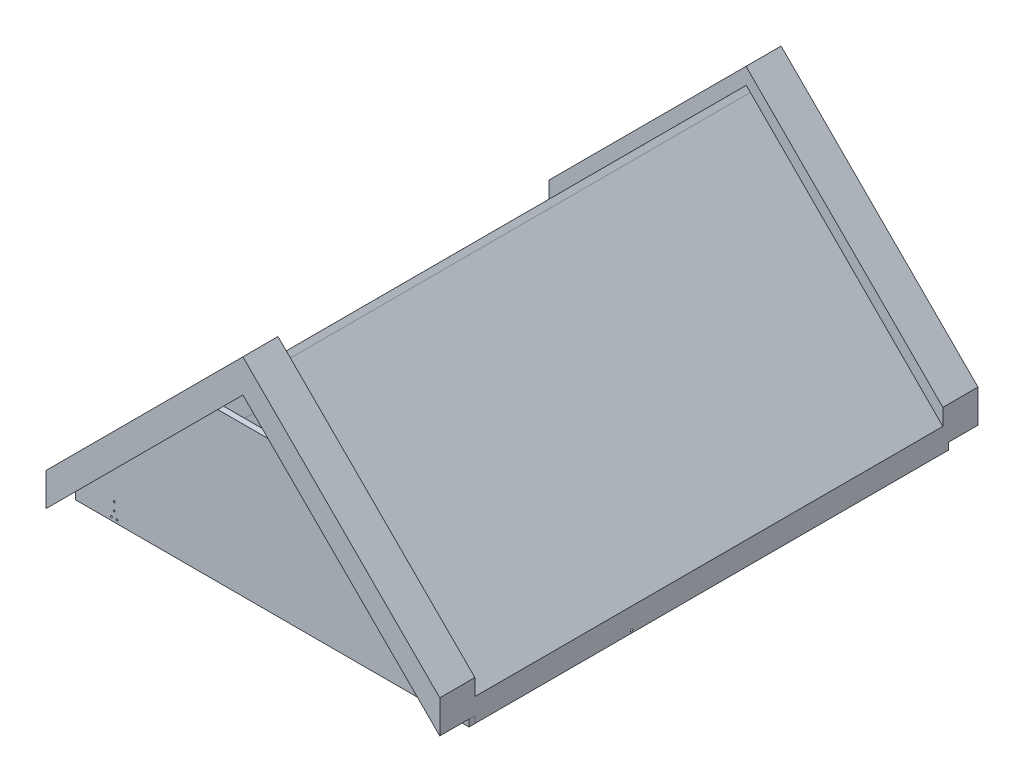
SolidWorks part; units mm, degrees
material "Pine"
ref_plane "Front Plane" through (0, 0, 0) normal (0, 0, 1) x (1, 0, 0)
ref_plane "Top Plane" through (0, 0, 0) normal (0, 1, 0) x (1, 0, 0)
ref_plane "Right Plane" through (0, 0, 0) normal (1, 0, 0) x (0, 0, -1)
sketch "Sketch1" plane through (0, 0, 0) normal (0, 0, 1) x (1, 0, 0)
  line L0 (0, 0) -> (1400, 0)
  line L1 (700, 0) -> (700, 700)
  line L2 (700, 700) -> (0, 0)
  line L3 (700, 700) -> (1400, 0)
  dimension "D1" = 1400
  dimension "D2" = 700
extrude "Boss-Extrude1" add sketch "Sketch1" along normal blind 2000 contours L3 L0 L2
shell "Shell1" thickness 10 removed face at (700, 0, 1000)
sketch "Sketch2" plane through (0, 0, 0) normal (0, -1, 0) x (1, 0, 0)
  line L0 (0, 2000) -> (1400, 2000) construction
  line L1 (-150, 2150) -> (1550, 2150)
  line L2 (-150, 2150) -> (-150, -150)
  line L3 (-150, -150) -> (1550, -150)
  line L4 (1550, 2150) -> (1550, -150)
  line L5 (0, 2000) -> (0, 0) construction
  dimension "D1" = 1700
  dimension "D2" = 2300
  dimension "D3" = 150
  dimension "D4" = 150
sketch "Sketch3" plane through (0, 0, 0) normal (-0.7071, 0.7071, 0) x (0, 0, 1)
  line L10 (2150, 1096.0155) -> (2000, 1096.0155)
  line L11 (2150, 1096.0155) -> (2150, 0)
  line L12 (2150, 0) -> (2000, 0)
  line L13 (2000, 1096.0155) -> (2000, 0)
extrude "Boss-Extrude2" add sketch "Sketch3" along normal blind 100 separate body contours L11 L10 L13 L12
sketch "Sketch7" plane through (700, 700, 0) normal (0.7071, 0.7071, 0) x (0, 0, -1)
  line L5 (-2150, 100) -> (-2000, 100)
  line L6 (-2150, 100) -> (-2150, -989.9495)
  line L7 (-2150, -989.9495) -> (-2000, -989.9495)
  line L8 (-2000, 100) -> (-2000, -989.9495)
extrude "Boss-Extrude4" add sketch "Sketch7" along normal blind 100
sketch "Sketch8" plane through (775, 775, 0) normal (0.7071, 0.7071, 0) x (0, 0, -1)
  line L1 (-2000, 100) -> (-2150, 100)
  line L2 (-2000, 100) -> (-2000, 0)
  line L3 (-2000, 0) -> (-2150, 0)
  line L4 (-2150, 100) -> (-2150, 0)
extrude "Cut-Extrude1" cut sketch "Sketch8" against normal up to vertex (6.066 mm away) and the other way blind 6 up to point (770.7107, 770.7107, 2150)
sketch "Sketch9" plane through (0, 0, 0) normal (-0.7071, -0.7071, 0) x (0, 0, 1)
  line L2 (2000, 100) -> (2150, 100)
  line L3 (2000, 100) -> (2000, 0)
  line L4 (2000, 0) -> (2150, 0)
  line L5 (2150, 100) -> (2150, 0)
extrude "Boss-Extrude5" add sketch "Sketch9" along normal blind 239.05
sketch "Sketch10" plane through (700, -700, 0) normal (0.7071, -0.7071, 0) x (0, 0, -1)
  line L1 (-2000, 989.9495) -> (-2150, 989.9495)
  line L2 (-2000, 989.9495) -> (-2000, 1089.9495)
  line L3 (-2000, 1089.9495) -> (-2150, 1089.9495)
  line L4 (-2150, 989.9495) -> (-2150, 1089.9495)
extrude "Boss-Extrude6" add sketch "Sketch10" along normal blind 399.5
sketch "Sketch13" plane through (0, 0, 2150) normal (0, 0, 1) x (1, 0, 0)
  line L0 (-141.4214, 0) -> (-141.4214, -141.4214)
  line L1 (-150, 0) -> (1550, 0) construction
  line L2 (700, 841.4214) -> (-239.7446, -98.3232) construction
  line L3 (700, 700) -> (-169.0339, -169.0339) construction
  line L4 (-141.4214, -141.4214) -> (-169.0339, -169.0339)
  line L5 (-169.0339, -169.0339) -> (-239.7446, -98.3232)
  line L6 (-239.7446, -98.3232) -> (-141.4214, 0)
  line L7 (1541.4214, 0) -> (1753.1998, -211.7785)
  line L8 (700, 841.4214) -> (1753.1998, -211.7785) construction
  line L9 (1753.1998, -211.7785) -> (1682.4892, -282.4892)
  line L10 (1682.4892, -282.4892) -> (1541.2446, -141.2446)
  line L12 (1541.4214, 0) -> (1541.2446, -141.2446)
extrude "Cut-Extrude4" cut sketch "Sketch13" against normal blind 1197.5
ref_plane "Plane1" through (0, 0, 1000) normal (0, 0, 1) x (1, 0, 0)
mirror "Mirror4" about plane through (0, 0, 1000) normal (0, 0, 1) of bodies 114 108
sketch "Sketch14" plane through (-141.4214, 0, 0) normal (-1, 0, 0) x (0, 0, 1)
  line L0 (0, -141.4214) -> (0, 0) construction
  line L5 (0, -70.7107) -> (2000, -70.7107)
  line L6 (0, -70.7107) -> (0, -170.7107)
  line L7 (0, -170.7107) -> (2000, -170.7107)
  line L8 (2000, -70.7107) -> (2000, -170.7107)
  dimension "D1" = 100
  dimension "D2" = 70.7107
  dimension "D3" = 2000
extrude "Boss-Extrude7" add sketch "Sketch14" against normal blind 25
sketch "Sketch15" plane through (1541.4189, -1.9292, 0) normal (1, -0.0013, 0) x (0, 0, -1)
  line L0 (-2000, 1.9292) -> (-2000, -139.3155) construction
  line L2 (-2000, -68.6932) -> (-2000, -70.8563)
  line L4 (0, -68.6932) -> (0, -70.8563)
  line L6 (-2000, -68.6932) -> (0, -68.6932)
  line L7 (-2000, -68.6932) -> (-2000, -168.6932)
  line L8 (-2000, -168.6932) -> (0, -168.6932)
  line L9 (0, -68.6932) -> (0, -168.6932)
  dimension "D1" = 100
extrude "Boss-Extrude8" add sketch "Sketch15" against normal blind 25 contours L7 L6 L9 L8
ref_plane "Plane2" through (-106.066, -106.066, 0) normal (0.7071, 0.7071, 0) x (0, 0, -1)
sketch "Sketch16" plane through (-106.066, -106.066, 0) normal (0.7071, 0.7071, 0) x (0, 0, -1)
  line L0 (0, -1089.9495) -> (0, 100) construction
  line L1 (-2000, 50) -> (0, 50)
  line L2 (-2000, 50) -> (-2000, 25)
  line L3 (-2000, 25) -> (0, 25)
  line L4 (0, 50) -> (0, 25)
  line L5 (-2000, 50) -> (0, 50) construction
  dimension "D1" = 25
  dimension "D2" = 2000
extrude "Boss-Extrude9" add sketch "Sketch16" along normal blind 1436
ref_plane "Plane3" through (804.0484, -806.0636, 0) normal (-0.7062, 0.708, 0) x (0.708, 0.7062, 0)
sketch "Sketch17" plane through (804.0484, -806.0636, 0) normal (-0.7062, 0.708, 0) x (0.708, 0.7062, 0)
  line L0 (1091.3128, 0) -> (1089.9174, 0) construction
  line L1 (1041.3752, 0) -> (1016.3752, 0)
  line L2 (1041.3752, 0) -> (1041.3752, -2000)
  line L3 (1041.3752, -2000) -> (1016.3752, -2000)
  line L4 (1016.3752, 0) -> (1016.3752, -2000)
  dimension "D1" = 25
  dimension "D2" = 2000
extrude "Boss-Extrude10" add sketch "Sketch17" along normal blind 1436
sketch "Sketch25" plane through (-35.3553, 35.3553, 0) normal (-0.7071, 0.7071, 0) x (0, 0, 1)
  line L6 (0, 1041.4386) -> (2000, 1041.4386)
  line L7 (2000, 1041.4386) -> (2000, 1089.9495)
  line L8 (2000, 1089.9495) -> (2000, 1286)
  line L9 (2000, 1286) -> (0, 1286)
  line L10 (0, 1286) -> (0, 1089.9495)
  line L11 (0, 1089.9495) -> (0, 1041.4386)
  line L12 (0, 1041.4386) -> (2000, 1041.4386)
  line L13 (2000, 1041.4386) -> (2000, 1089.9495)
  line L14 (2000, 1089.9495) -> (2000, 1286)
  line L15 (2000, 1286) -> (0, 1286)
  line L16 (0, 1286) -> (0, 1089.9495)
  line L17 (0, 1089.9495) -> (0, 1041.4386)
  dimension "D1" = 0
sketch "Sketch26" plane through (737.2845, 735.4413, 0) normal (0.708, 0.7062, 0) x (0, 0, -1)
  line L6 (-2000, 101.3034) -> (-2000, 51.3034)
  line L7 (-2000, 51.3034) -> (0, 51.3034)
  line L8 (0, 51.3034) -> (0, 101.3034)
  line L9 (0, 101.3034) -> (0, 297.478)
  line L10 (0, 297.478) -> (-2000, 297.478)
  line L11 (-2000, 297.478) -> (-2000, 101.3034)
  line L12 (-2000, 101.3034) -> (-2000, 51.3034)
  line L14 (0, 51.3034) -> (0, 101.3034)
  line L15 (0, 101.3034) -> (0, 297.478)
  line L16 (0, 297.478) -> (-2000, 297.478)
  line L17 (-2000, 297.478) -> (-2000, 101.3034)
  line L18 (-2000, 51.3034) -> (0, 51.3034)
  dimension "D1" = 0
sketch "Sketch27" plane through (719.5847, 717.7858, 0) normal (-0.708, -0.7062, 0) x (0, 0, 1)
  line L6 (0, 101.2721) -> (0, 51.2721)
  line L7 (0, 51.2721) -> (2000, 51.2721)
  line L8 (2000, 51.2721) -> (2000, 101.2721)
  line L9 (2000, 101.2721) -> (2000, 297.478)
  line L10 (2000, 297.478) -> (0, 297.478)
  line L11 (0, 297.478) -> (0, 101.2721)
  line L12 (0, 101.2721) -> (0, 51.2721)
  line L13 (0, 51.2721) -> (2000, 51.2721)
  line L14 (2000, 51.2721) -> (2000, 101.2721)
  line L15 (2000, 101.2721) -> (2000, 297.478)
  line L16 (2000, 297.478) -> (0, 297.478)
  line L17 (0, 297.478) -> (0, 101.2721)
  dimension "D1" = 0
extrude "Cut-Extrude11" cut sketch "Sketch27" against normal blind 1286
sketch "Sketch28" plane through (-17.6777, 17.6777, 0) normal (0.7071, -0.7071, 0) x (0, 0, -1)
  line L6 (-2000, 1041.4073) -> (0, 1041.4073)
  line L7 (0, 1041.4073) -> (0, 1089.9495)
  line L8 (0, 1089.9495) -> (0, 1286)
  line L9 (0, 1286) -> (-2000, 1286)
  line L10 (-2000, 1286) -> (-2000, 1089.9495)
  line L11 (-2000, 1089.9495) -> (-2000, 1041.4073)
  line L12 (-2000, 1041.4073) -> (0, 1041.4073)
  line L13 (0, 1041.4073) -> (0, 1089.9495)
  line L14 (0, 1089.9495) -> (0, 1286)
  line L15 (0, 1286) -> (-2000, 1286)
  line L16 (-2000, 1286) -> (-2000, 1089.9495)
  line L17 (-2000, 1089.9495) -> (-2000, 1041.4073)
  dimension "D1" = 0
extrude "Cut-Extrude12" cut sketch "Sketch28" against normal blind 1286
sketch "Sketch29" plane through (0, 0, 2000) normal (0, 0, -1) x (-1, 0, 0)
  line L1 (-701.0308, 594.9648) -> (-1466.5902, -170.5946)
  line L2 (-630.3202, 665.6755) -> (116.4214, -81.066)
  line L4 (-701.0308, 594.9648) -> (64.6409, -170.7069)
  line L5 (116.4214, -170.7107) -> (64.6409, -170.7069)
  line L6 (116.4214, -81.066) -> (-701.0308, 736.3862)
  line L7 (-701.0308, 736.3862) -> (-1516.32, -80.9463)
  line L8 (-1516.32, -80.9463) -> (-1516.2758, -116.2758)
  line L9 (-1516.2758, -116.2758) -> (-700, 700)
  line L10 (-700, 700) -> (116.4214, -116.4214)
  line L11 (116.4214, -116.4214) -> (116.4214, -81.066)
  line L12 (-630.3202, 665.6755) -> (-701.0308, 736.3862)
  line L13 (-701.0308, 736.3862) -> (-1516.32, -80.9463)
  line L18 (-1466.5902, -170.5946) -> (-1516.2078, -170.5909)
  line L19 (-1516.32, -80.9463) -> (-1516.2078, -170.5909)
  line L20 (116.4214, -81.066) -> (116.4214, -170.7107)
  dimension "D2" = 100
  dimension "D3" = 100
  dimension "D1" = 0
extrude "Boss-Extrude13" add sketch "Sketch29" along normal blind 50
ref_plane "Plane4" through (0, 0, 1359) normal (0, 0, -1) x (-1, 0, 0)
sketch "Sketch30" plane through (0, 0, 1359) normal (0, 0, -1) x (-1, 0, 0)
  line L8 (-701.0308, 736.3862) -> (-1516.32, -80.9463)
  line L9 (-701.0308, 736.3862) -> (-1516.32, -80.9463)
  line L10 (-1516.2078, -170.5909) -> (-1466.5902, -170.5946)
  line L11 (-1466.5902, -170.5946) -> (-701.0308, 594.9648)
  line L12 (-701.0308, 594.9648) -> (64.6409, -170.7069)
  line L13 (64.6409, -170.7069) -> (116.4214, -170.7107)
  line L14 (-1516.32, -80.9463) -> (-1516.2078, -170.5909)
  line L15 (-1516.32, -80.9463) -> (-1516.2078, -170.5909)
  line L18 (-1516.2078, -170.5909) -> (-1466.5902, -170.5946)
  line L19 (-1466.5902, -170.5946) -> (-701.0308, 594.9648)
  line L20 (-701.0308, 594.9648) -> (64.6409, -170.7069)
  line L21 (64.6409, -170.7069) -> (116.4214, -170.7107)
  line L24 (116.4214, -170.7107) -> (116.4214, -81.066)
  line L25 (116.4214, -170.7107) -> (116.4214, -81.066)
  line L26 (116.4214, -81.066) -> (-701.0308, 736.3862)
  line L27 (116.4214, -81.066) -> (-701.0308, 736.3862)
  dimension "D1" = 0
extrude "Boss-Extrude14" add sketch "Sketch30" along normal blind 50
ref_plane "Plane5" through (0, 0, 691) normal (0, 0, -1) x (-1, 0, 0)
sketch "Sketch31" plane through (0, 0, 691) normal (0, 0, -1) x (-1, 0, 0)
  line L8 (116.4214, -81.066) -> (-701.0308, 736.3862)
  line L9 (-701.0308, 736.3862) -> (-1516.32, -80.9463)
  line L10 (-1516.32, -80.9463) -> (-1516.2078, -170.5909)
  line L11 (-1516.2078, -170.5909) -> (-1466.5902, -170.5946)
  line L12 (-1466.5902, -170.5946) -> (-701.0308, 594.9648)
  line L13 (-701.0308, 594.9648) -> (64.6409, -170.7069)
  line L14 (64.6409, -170.7069) -> (116.4214, -170.7107)
  line L15 (116.4214, -170.7107) -> (116.4214, -81.066)
  line L16 (116.4214, -81.066) -> (-701.0308, 736.3862)
  line L17 (-701.0308, 736.3862) -> (-1516.32, -80.9463)
  line L18 (-1516.32, -80.9463) -> (-1516.2078, -170.5909)
  line L19 (-1516.2078, -170.5909) -> (-1466.5902, -170.5946)
  line L20 (-1466.5902, -170.5946) -> (-701.0308, 594.9648)
  line L21 (-701.0308, 594.9648) -> (64.6409, -170.7069)
  line L22 (64.6409, -170.7069) -> (116.4214, -170.7107)
  line L23 (116.4214, -170.7107) -> (116.4214, -81.066)
  dimension "D1" = 0
extrude "Boss-Extrude15" add sketch "Sketch31" along normal blind 50
ref_plane "Plane6" through (0, 0, 50) normal (0, 0, -1) x (-1, 0, 0)
sketch "Sketch33" plane through (0, 0, 50) normal (0, 0, -1) x (-1, 0, 0)
  line L8 (116.4214, -170.7107) -> (116.4214, -81.066)
  line L9 (116.4214, -81.066) -> (-701.0308, 736.3862)
  line L10 (-701.0308, 736.3862) -> (-1516.32, -80.9463)
  line L11 (-1516.32, -80.9463) -> (-1516.2078, -170.5909)
  line L12 (-1516.2078, -170.5909) -> (-1466.5902, -170.5946)
  line L13 (-1466.5902, -170.5946) -> (-701.0308, 594.9648)
  line L14 (-701.0308, 594.9648) -> (64.6409, -170.7069)
  line L15 (64.6409, -170.7069) -> (116.4214, -170.7107)
  line L16 (116.4214, -170.7107) -> (116.4214, -81.066)
  line L17 (116.4214, -81.066) -> (-701.0308, 736.3862)
  line L18 (-701.0308, 736.3862) -> (-1516.32, -80.9463)
  line L19 (-1516.32, -80.9463) -> (-1516.2078, -170.5909)
  line L20 (-1516.2078, -170.5909) -> (-1466.5902, -170.5946)
  line L21 (-1466.5902, -170.5946) -> (-701.0308, 594.9648)
  line L22 (-701.0308, 594.9648) -> (64.6409, -170.7069)
  line L23 (64.6409, -170.7069) -> (116.4214, -170.7107)
  dimension "D1" = 0
extrude "Boss-Extrude16" add sketch "Sketch33" along normal blind 50
sketch "Sketch35" plane through (0, 0, 2000) normal (0, 0, 1) x (1, 0, 0)
  line L0 (60.3572, -45.7088) -> (1341.7044, -45.7088)
  line L1 (701.0308, 594.9648) -> (-64.6409, -170.7069) construction
  line L2 (-39.6428, -145.7088) -> (1441.7044, -145.7088)
  line L3 (1466.5902, -170.5946) -> (701.0308, 594.9648) construction
  line L4 (60.3572, -45.7088) -> (-39.6428, -145.7088)
  line L5 (1341.7044, -45.7088) -> (1441.7044, -145.7088)
  line L9 (-64.6409, -170.7069) -> (-116.4214, -170.7107) construction
  line L10 (-64.6409, -170.7069) -> (-116.4214, -170.7107)
  point P10 (-90.5311, -170.7088)
  line M8 (-64.6409, -170.7069) -> (701.0308, 594.9648)
  line M9 (701.0308, 594.9648) -> (1466.5902, -170.5946)
  dimension "D1" = 100
  dimension "D2" = 25
extrude "Boss-Extrude17" add sketch "Sketch35" against normal blind 50 separate body contours L2 L0 M8 M9 region at (701.0308, -96.9153, 2000)
sketch "Sketch36" plane through (0, 0, 1359) normal (0, 0, -1) x (-1, 0, 0)
  line L4 (39.6428, -145.7088) -> (-60.3572, -45.7088)
  line L5 (-60.3572, -45.7088) -> (-1341.7044, -45.7088)
  line L6 (-1341.7044, -45.7088) -> (-1441.7044, -145.7088)
  line L7 (-1441.7044, -145.7088) -> (39.6428, -145.7088)
  line L8 (39.6428, -145.7088) -> (-60.3572, -45.7088)
  line L9 (-60.3572, -45.7088) -> (-1341.7044, -45.7088)
  line L10 (-1341.7044, -45.7088) -> (-1441.7044, -145.7088)
  line L11 (-1441.7044, -145.7088) -> (39.6428, -145.7088)
  dimension "D1" = 0
extrude "Boss-Extrude18" add sketch "Sketch36" along normal blind 50 separate body
sketch "Sketch37" plane through (0, 0, 691) normal (0, 0, -1) x (-1, 0, 0)
  line L4 (-1441.7044, -145.7088) -> (39.6428, -145.7088)
  line L5 (39.6428, -145.7088) -> (-60.3572, -45.7088)
  line L6 (-60.3572, -45.7088) -> (-1341.7044, -45.7088)
  line L7 (-1341.7044, -45.7088) -> (-1441.7044, -145.7088)
  line L8 (-1441.7044, -145.7088) -> (39.6428, -145.7088)
  line L9 (39.6428, -145.7088) -> (-60.3572, -45.7088)
  line L10 (-60.3572, -45.7088) -> (-1341.7044, -45.7088)
  line L11 (-1341.7044, -45.7088) -> (-1441.7044, -145.7088)
  dimension "D1" = 0
extrude "Boss-Extrude19" add sketch "Sketch37" along normal blind 50 separate body
sketch "Sketch38" plane through (0, 0, 50) normal (0, 0, -1) x (-1, 0, 0)
  line L4 (-1341.7044, -45.7088) -> (-1441.7044, -145.7088)
  line L5 (-1441.7044, -145.7088) -> (39.6428, -145.7088)
  line L6 (39.6428, -145.7088) -> (-60.3572, -45.7088)
  line L7 (-60.3572, -45.7088) -> (-1341.7044, -45.7088)
  line L8 (-1341.7044, -45.7088) -> (-1441.7044, -145.7088)
  line L9 (-1441.7044, -145.7088) -> (39.6428, -145.7088)
  line L10 (39.6428, -145.7088) -> (-60.3572, -45.7088)
  line L11 (-60.3572, -45.7088) -> (-1341.7044, -45.7088)
  dimension "D1" = 0
extrude "Boss-Extrude20" add sketch "Sketch38" along normal blind 50 separate body
sketch "Sketch34" plane through (0.0125, -170.7021, 0) normal (0.0001, -1, 0) x (1, 0.0001, 0)
  line L0 (1441.6938, 1950) -> (1441.6938, 2000) construction
  line L5 (1.0188, 2000) -> (1401.0188, 2000)
  line L6 (1.0188, 2000) -> (1.0188, 0)
  line L7 (1.0188, 0) -> (1401.0188, 0)
  line L8 (1401.0188, 2000) -> (1401.0188, 0)
  line L9 (-39.6534, 2000) -> (1441.6938, 2000) construction
  dimension "D1" = 1400
  dimension "D2" = 2000
  dimension "D3" = 40.675
extrude "Boss-Extrude21" add sketch "Sketch34" against normal blind 25 separate body
sketch "Sketch39" plane through (0, 0, 2000) normal (0, 0, 1) x (1, 0, 0)
  line L0 (-64.6409, -170.7069) -> (1466.5902, -170.5946)
  line L1 (467.5, 467.5) -> (932.5, 467.5)
  line L10 (-141.4214, -170.7107) -> (-116.4214, -170.7107)
  line L11 (-116.4214, -170.7107) -> (-64.6409, -170.7069)
  line L12 (-64.6409, -170.7069) -> (701.0308, 594.9648)
  line L13 (701.0308, 594.9648) -> (1466.5902, -170.5946)
  line L14 (1466.5902, -170.5946) -> (1516.2078, -170.5909)
  line L15 (1516.2078, -170.5909) -> (1541.2078, -170.6222)
  line L16 (1541.2078, -170.6222) -> (1541.2446, -141.2446)
  line L17 (1541.2446, -141.2446) -> (700, 700)
  line L18 (700, 700) -> (-141.4214, -141.4214)
  line L19 (-141.4214, -141.4214) -> (-141.4214, -170.7107)
  line L20 (-141.4214, -170.7107) -> (-116.4214, -170.7107)
  line L21 (-116.4214, -170.7107) -> (-64.6409, -170.7069)
  line L24 (1466.5902, -170.5946) -> (1516.2078, -170.5909)
  line L25 (1516.2078, -170.5909) -> (1541.2078, -170.6222)
  line L26 (1541.2078, -170.6222) -> (1541.2446, -141.2446)
  line L27 (1541.2446, -141.2446) -> (932.5, 467.5)
  line L28 (467.5, 467.5) -> (-141.4214, -141.4214)
  line L29 (-141.4214, -141.4214) -> (-141.4214, -170.7107)
  dimension "D2" = 465
  dimension "D1" = 0
extrude "Boss-Extrude22" add sketch "Sketch39" along normal blind 25 separate body
sketch "Sketch40" plane through (0, 0, 0) normal (0, 0, -1) x (-1, 0, 0)
  line L0 (-1466.5902, -170.5946) -> (64.6409, -170.7069)
  line L2 (-932.5, 467.5) -> (-467.5, 467.5)
  line L10 (141.4214, -170.7107) -> (141.4214, -141.4214)
  line L11 (141.4214, -141.4214) -> (-700, 700)
  line L12 (-700, 700) -> (-1541.2446, -141.2446)
  line L13 (-1541.2446, -141.2446) -> (-1541.2078, -170.6222)
  line L14 (-1541.2078, -170.6222) -> (-1516.2078, -170.5909)
  line L15 (-1516.2078, -170.5909) -> (-1466.5902, -170.5946)
  line L16 (-1466.5902, -170.5946) -> (-701.0308, 594.9648)
  line L17 (-701.0308, 594.9648) -> (64.6409, -170.7069)
  line L18 (64.6409, -170.7069) -> (116.4214, -170.7107)
  line L19 (116.4214, -170.7107) -> (141.4214, -170.7107)
  line L20 (141.4214, -170.7107) -> (141.4214, -141.4214)
  line L21 (141.4214, -141.4214) -> (-467.5, 467.5)
  line L22 (-932.5, 467.5) -> (-1541.2446, -141.2446)
  line L23 (-1541.2446, -141.2446) -> (-1541.2078, -170.6222)
  line L24 (-1541.2078, -170.6222) -> (-1516.2078, -170.5909)
  line L25 (-1516.2078, -170.5909) -> (-1466.5902, -170.5946)
  line L28 (64.6409, -170.7069) -> (116.4214, -170.7107)
  line L29 (116.4214, -170.7107) -> (141.4214, -170.7107)
  dimension "D2" = 465
  dimension "D1" = 0
extrude "Boss-Extrude23" add sketch "Sketch40" along normal blind 25
sketch "Sketch41" plane through (0.0125, -170.7021, 0) normal (0.0001, -1, 0) x (1, 0.0001, 0)
  line L0 (12.3035, 1864.4107) -> (16.9035, 1864.4244)
  line L1 (1.0015, 1999.9778) -> (12.3035, 1864.4107)
  line L2 (0.9765, 2008.4278) -> (1.0015, 1999.9778)
  line L3 (9.9764, 2008.4544) -> (0.9765, 2008.4278)
  line L4 (10.0015, 2000.0045) -> (9.9764, 2008.4544)
  line L5 (27.8014, 2000.0573) -> (10.0015, 2000.0045)
  line L6 (27.7764, 2008.5072) -> (27.8014, 2000.0573)
  line L7 (36.7763, 2008.5339) -> (27.7764, 2008.5072)
  line L8 (36.8014, 2000.084) -> (36.7763, 2008.5339)
  line L9 (26.3034, 1864.4523) -> (36.8014, 2000.084)
  line L10 (21.7034, 1864.4386) -> (26.3034, 1864.4523)
  line L77 (1376.4806, 1864.3486) -> (1381.0806, 1864.3622)
  line L78 (1365.1787, 1999.9157) -> (1376.4806, 1864.3486)
  line L79 (1365.1536, 2008.3656) -> (1365.1787, 1999.9157)
  line L80 (1374.1536, 2008.3923) -> (1365.1536, 2008.3656)
  line L81 (1374.1786, 1999.9423) -> (1374.1536, 2008.3923)
  line L82 (1391.9786, 1999.9951) -> (1374.1786, 1999.9423)
  line L83 (1391.9535, 2008.445) -> (1391.9786, 1999.9951)
  line L84 (1400.9535, 2008.4717) -> (1391.9535, 2008.445)
  line L85 (1400.9785, 2000.0218) -> (1400.9535, 2008.4717)
  line L86 (1390.4806, 1864.3901) -> (1400.9785, 2000.0218)
  line L87 (1385.8806, 1864.3764) -> (1390.4806, 1864.3901)
  spline S0 degree 3 poles (27.8669, 1977.9724) (22.8369, 1977.9575) (22.8518, 1972.9275) (27.8818, 1972.9424) (32.9118, 1972.9573) (32.8969, 1977.9873) (27.8669, 1977.9724) (22.8369, 1977.9575) (22.8518, 1972.9275) knots -0.5 0 0 0 0.5 0.5 0.5 1 1 1 1.5 1.5 1.5 weights 1 0.333333 0.333333 1 0.333333 0.333333 1 0.333333 0.333333 only from (27.8669, 1977.9724) to (27.8669, 1977.9724)
  spline S1 degree 3 poles (19.1096, 1929.8312) (14.3096, 1929.817) (14.3238, 1925.017) (19.1238, 1925.0312) (23.9238, 1925.0455) (23.9095, 1929.8454) (19.1096, 1929.8312) (14.3096, 1929.817) (14.3238, 1925.017) knots -0.5 0 0 0 0.5 0.5 0.5 1 1 1 1.5 1.5 1.5 weights 1 0.333333 0.333333 1 0.333333 0.333333 1 0.333333 0.333333 only from (19.1096, 1929.8312) to (19.1096, 1929.8312)
  spline S32 degree 3 poles (19.2519, 1881.8314) (14.4519, 1881.8172) (14.4661, 1877.0172) (19.2661, 1877.0314) (24.0661, 1877.0457) (24.0518, 1881.8457) (19.2519, 1881.8314) (14.4519, 1881.8172) (14.4661, 1877.0172) knots -0.5 0 0 0 0.5 0.5 0.5 1 1 1 1.5 1.5 1.5 weights 1 0.333333 0.333333 1 0.333333 0.333333 1 0.333333 0.333333 only from (19.2519, 1881.8314) to (19.2519, 1881.8314)
  spline S33 degree 3 poles (10.0366, 1988.1686) (4.5086, 1988.1522) (4.525, 1982.6242) (10.053, 1982.6406) (15.581, 1982.657) (15.5646, 1988.185) (10.0366, 1988.1686) (4.5086, 1988.1522) (4.525, 1982.6242) knots -0.5 0 0 0 0.5 0.5 0.5 1 1 1 1.5 1.5 1.5 weights 1 0.333333 0.333333 1 0.333333 0.333333 1 0.333333 0.333333 only from (10.0366, 1988.1686) to (10.0366, 1988.1686)
  spline S34 degree 3 poles (16.9035, 1864.4244) (16.9177, 1859.6244) (21.7177, 1859.6386) (21.7034, 1864.4386) knots 0 0 0 0 1 1 1 1 weights 1 0.333333 0.333333 1
  spline S35 degree 3 poles (1392.044, 1977.9102) (1387.014, 1977.8953) (1387.029, 1972.8653) (1392.0589, 1972.8802) (1397.0889, 1972.8951) (1397.074, 1977.9251) (1392.044, 1977.9102) (1387.014, 1977.8953) (1387.029, 1972.8653) knots -0.5 0 0 0 0.5 0.5 0.5 1 1 1 1.5 1.5 1.5 weights 1 0.333333 0.333333 1 0.333333 0.333333 1 0.333333 0.333333 only from (1392.044, 1977.9102) to (1392.044, 1977.9102)
  spline S36 degree 3 poles (1383.2867, 1929.769) (1378.4867, 1929.7548) (1378.501, 1924.9548) (1383.3009, 1924.969) (1388.1009, 1924.9833) (1388.0867, 1929.7833) (1383.2867, 1929.769) (1378.4867, 1929.7548) (1378.501, 1924.9548) knots -0.5 0 0 0 0.5 0.5 0.5 1 1 1 1.5 1.5 1.5 weights 1 0.333333 0.333333 1 0.333333 0.333333 1 0.333333 0.333333 only from (1383.2867, 1929.769) to (1383.2867, 1929.769)
  spline S37 degree 3 poles (1383.429, 1881.7692) (1378.629, 1881.755) (1378.6433, 1876.955) (1383.4432, 1876.9693) (1388.2432, 1876.9835) (1388.229, 1881.7835) (1383.429, 1881.7692) (1378.629, 1881.755) (1378.6433, 1876.955) knots -0.5 0 0 0 0.5 0.5 0.5 1 1 1 1.5 1.5 1.5 weights 1 0.333333 0.333333 1 0.333333 0.333333 1 0.333333 0.333333 only from (1383.429, 1881.7692) to (1383.429, 1881.7692)
  spline S38 degree 3 poles (1374.2137, 1988.1064) (1368.6857, 1988.09) (1368.7021, 1982.562) (1374.2301, 1982.5784) (1379.7581, 1982.5948) (1379.7417, 1988.1228) (1374.2137, 1988.1064) (1368.6857, 1988.09) (1368.7021, 1982.562) knots -0.5 0 0 0 0.5 0.5 0.5 1 1 1 1.5 1.5 1.5 weights 1 0.333333 0.333333 1 0.333333 0.333333 1 0.333333 0.333333 only from (1374.2137, 1988.1064) to (1374.2137, 1988.1064)
  spline S39 degree 3 poles (1381.0806, 1864.3622) (1381.0948, 1859.5622) (1385.8948, 1859.5764) (1385.8806, 1864.3764) knots 0 0 0 0 1 1 1 1 weights 1 0.333333 0.333333 1
extrude "Cut-Extrude14" [suppressed] cut sketch "Sketch41" against normal blind 10 contours S33 | S0 | S1 | S36 | S35 | S38
ref_plane "Plane7" through (0, 0, 2010) normal (0, 0, 1) x (1, 0, 0)
sketch "Sketch42" plane through (0, 0, 2010) normal (0, 0, 1) x (-1, 0, 0)
  line L88 (-1349.3821, 25.2633) -> (-1353.982, 25.2497)
  line L89 (-1353.982, 25.2497) -> (-1362.944, 132.749)
  line L90 (-1362.944, 132.749) -> (-1363.0523, 169.2734)
  line L91 (-1363.0523, 169.2734) -> (-1356.3091, 169.2934)
  line L92 (-1356.3091, 169.2934) -> (-1356.284, 160.8434)
  line L93 (-1356.284, 160.8434) -> (-1338.5085, 160.8961)
  line L94 (-1338.5085, 160.8961) -> (-1338.5336, 169.3595)
  line L95 (-1331.5821, 133.8178) -> (-1339.9821, 25.2912)
  line L96 (-1339.9821, 25.2912) -> (-1344.5821, 25.2775)
  line L97 (-1331.5821, 133.8178) -> (-1331.7903, 169.3595)
  line L99 (-1331.7903, 169.3595) -> (-1338.5336, 169.3595)
  spline S2 degree 3 poles (-1344.5821, 25.2775) (-1344.5679, 20.4775) (-1349.3678, 20.4633) (-1349.3821, 25.2633) knots 0 0 0 0 1 1 1 1 weights 1 0.333333 0.333333 1
  spline S3 degree 3 poles (-1338.449, 149.0603) (-1332.921, 149.0766) (-1332.9047, 143.5487) (-1338.4326, 143.5323) (-1343.9606, 143.5159) (-1343.977, 149.0439) (-1338.449, 149.0603) (-1332.921, 149.0766) (-1332.9047, 143.5487) knots -0.5 0 0 0 0.5 0.5 0.5 1 1 1 1.5 1.5 1.5 weights 1 0.333333 0.333333 1 0.333333 0.333333 1 0.333333 0.333333 only from (-1338.449, 149.0603) to (-1338.449, 149.0603)
  spline S4 degree 3 poles (-1347.0337, 42.6703) (-1342.2337, 42.6846) (-1342.2194, 37.8846) (-1347.0194, 37.8704) (-1351.8194, 37.8561) (-1351.8336, 42.6561) (-1347.0337, 42.6703) (-1342.2337, 42.6846) (-1342.2194, 37.8846) knots -0.5 0 0 0 0.5 0.5 0.5 1 1 1 1.5 1.5 1.5 weights 1 0.333333 0.333333 1 0.333333 0.333333 1 0.333333 0.333333 only from (-1347.0337, 42.6703) to (-1347.0337, 42.6703)
  spline S5 degree 3 poles (-1347.176, 90.6701) (-1342.376, 90.6844) (-1342.3617, 85.8844) (-1347.1617, 85.8701) (-1351.9617, 85.8559) (-1351.9759, 90.6559) (-1347.176, 90.6701) (-1342.376, 90.6844) (-1342.3617, 85.8844) knots -0.5 0 0 0 0.5 0.5 0.5 1 1 1 1.5 1.5 1.5 weights 1 0.333333 0.333333 1 0.333333 0.333333 1 0.333333 0.333333 only from (-1347.176, 90.6701) to (-1347.176, 90.6701)
  spline S6 degree 3 poles (-1356.2186, 138.7585) (-1351.1886, 138.7734) (-1351.1737, 133.7435) (-1356.2036, 133.7285) (-1361.2336, 133.7136) (-1361.2485, 138.7436) (-1356.2186, 138.7585) (-1351.1886, 138.7734) (-1351.1737, 133.7435) knots -0.5 0 0 0 0.5 0.5 0.5 1 1 1 1.5 1.5 1.5 weights 1 0.333333 0.333333 1 0.333333 0.333333 1 0.333333 0.333333 only from (-1356.2186, 138.7585) to (-1356.2186, 138.7585)
  dimension "D1" = 1331.5821
  dimension "D2" = 1331.7903
  dimension "D3" = 1338.449
  dimension "D4" = 1338.5085
  dimension "D5" = 1338.5336
  dimension "D6" = 1339.9821
  dimension "D7" = 1344.5821
  dimension "D8" = 1347.0337
  dimension "D9" = 1347.176
  dimension "D10" = 1349.3821
  dimension "D11" = 1356.3091
  dimension "D12" = 1356.2186
  dimension "D13" = 1356.284
  dimension "D14" = 1363.0523
  dimension "D15" = 1362.944
  dimension "D16" = 25.2497
  dimension "D17" = 132.749
  dimension "D18" = 149.0603
  dimension "D20" = 42.6703
  dimension "D21" = 90.6701
  dimension "D23" = 133.8178
extrude "Cut-Extrude15" [suppressed] cut sketch "Sketch42" against normal blind 20
sketch "Sketch43" plane through (0, 0, 0) normal (1, 0, 0) x (0, 0, -1)
  line L0 (-2000, -170.6222) -> (25, -170.6222) construction
  line L1 (-2150, 0) -> (-2150, -141.2446) construction
  circle A0 centre (-1330, -160.6222) radius 5
  dimension "D1" = 10
  dimension "D2" = 10
  dimension "D3" = 820
extrude "Cut-Extrude16" cut sketch "Sketch43" against normal through all both and the other way through all
sketch "Sketch45" plane through (0, 0, 2000) normal (0, 0, 1) x (1, 0, 0)
  line L0 (1.0294, -145.7021) -> (1.0313, -170.7021) construction
  line L1 (13.0316, -156.2021) -> (37.0316, -156.2021) construction
  line L2 (5.0316, -175.7021) -> (45.0316, -175.7021) construction
  line L3 (25.0316, -175.7021) -> (25.0316, -156.2021) construction
  line L4 (25.0316, -156.2021) -> (25.0316, -129.2021) construction
  line L5 (25.0316, -129.2021) -> (25.0316, -95.2021) construction
  line L7 (1365.0316, -156.0997) -> (1389.0316, -156.0997) construction
  line L8 (1357.0316, -175.5997) -> (1397.0316, -175.5997) construction
  line L9 (1377.0316, -175.5997) -> (1377.0316, -156.0997) construction
  line L10 (1377.0316, -156.0997) -> (1377.0316, -129.0997) construction
  line L11 (1377.0316, -129.0997) -> (1377.0316, -95.0997) construction
  line L13 (1401.0294, -145.5994) -> (1401.0313, -170.5994) construction
  line L14 (1401.0313, -170.5994) -> (1.0313, -170.7021) construction
  circle A0 centre (13.0316, -156.2021) radius 4
  circle A1 centre (37.0316, -156.2021) radius 4
  circle A2 centre (25.0316, -129.2021) radius 4
  circle A3 centre (25.0316, -95.2021) radius 4
  circle A4 centre (1365.0316, -156.0997) radius 4
  circle A5 centre (1389.0316, -156.0997) radius 4
  circle A6 centre (1377.0316, -129.0997) radius 4
  circle A7 centre (1377.0316, -95.0997) radius 4
  point P11 (25.0316, -156.2021)
  point P24 (1377.0316, -156.0997)
  dimension "D6" = 8
  dimension "D8" = 8
  dimension "D10" = 8
  dimension "D14" = 8
  dimension "D16" = 8
  dimension "D18" = 8
  dimension "D1" = 4
  dimension "D2" = 40
  dimension "D3" = 19.5
  dimension "D4" = 5
  dimension "D5" = 24
  dimension "D7" = 27
  dimension "D9" = 34
  dimension "D11" = 40
  dimension "D12" = 19.5
  dimension "D13" = 24
  dimension "D15" = 27
  dimension "D17" = 34
  dimension "D19" = 4
  dimension "D20" = 5
extrude "Cut-Extrude17" cut sketch "Sketch45" along direction (0, 0, 1) on the side of the normal blind 30
